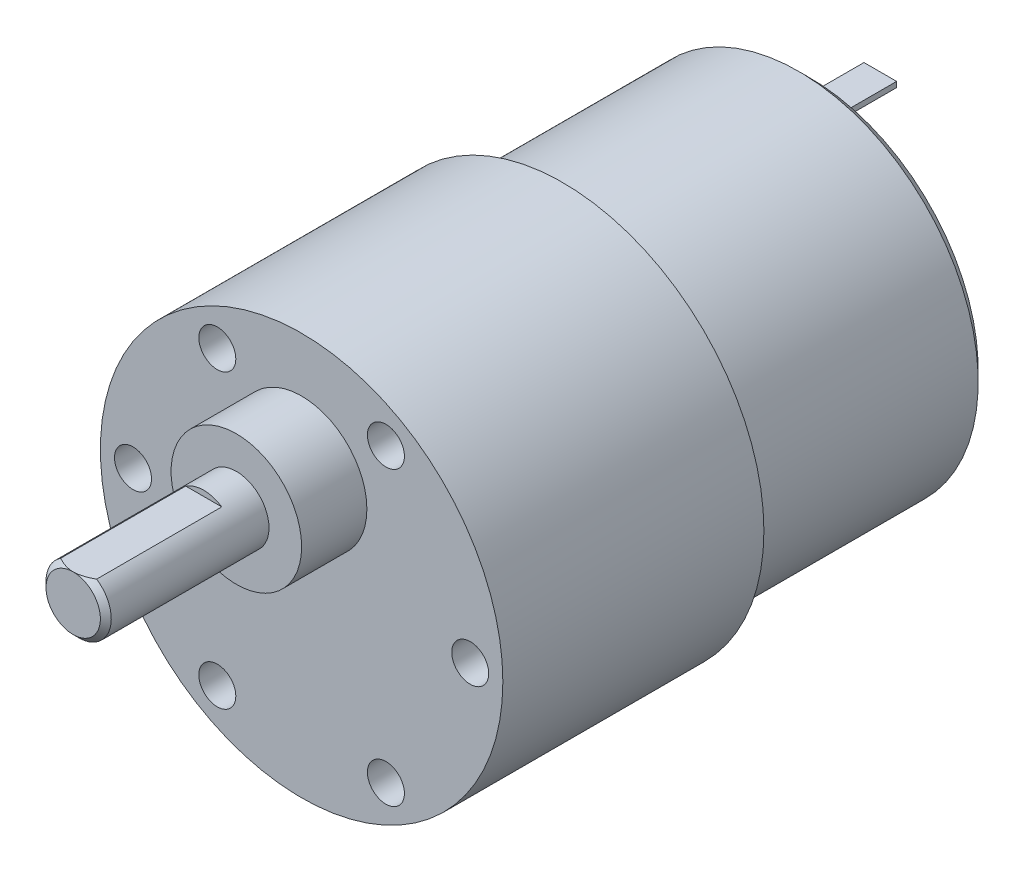
SolidWorks part; units mm, degrees
ref_plane "Front Plane" through (0, 0, 0) normal (0, 0, 1) x (1, 0, 0)
ref_plane "Top Plane" through (0, 0, 0) normal (0, 1, 0) x (1, 0, 0)
ref_plane "Right Plane" through (0, 0, 0) normal (1, 0, 0) x (0, 0, -1)
sketch "Sketch2" plane through (0, 0, 0) normal (0, 0, 1) x (1, 0, 0)
  circle A0 centre (0, 0) radius 18.5
  dimension "D1" = 37
extrude "Boss-Extrude1" add sketch "Sketch2" along normal blind 24
sketch "Sketch3" plane through (0, 0, 0) normal (0, 0, -1) x (-1, 0, 0)
  circle A0 centre (0, 0) radius 16.5
  dimension "D1" = 33
extrude "Boss-Extrude2" add sketch "Sketch3" along normal blind 22.7
sketch "Sketch4" plane through (0, 0, -22.7) normal (0, 0, -1) x (-1, 0, 0)
  circle A0 centre (0, 0) radius 3.75
  dimension "D1" = 7.5
extrude "Boss-Extrude3" add sketch "Sketch4" along normal blind 3.2
chamfer "Chamfer1" distance 1 angle 45 1 edges at (-16.5, 0, -22.7)
fillet "Fillet1" radius 1 1 edges at (-3.75, 0, -25.9)
sketch "Sketch5" plane through (0, 0, -22.7) normal (0, 0, -1) x (-1, 0, 0)
  line L0 (0, -12.45) -> (0, 12.45) construction
  line L2 (-1.5, 12.2) -> (1.5, 12.2)
  line L3 (-1.5, 12.2) -> (-1.5, 12.7)
  line L4 (-1.5, 12.7) -> (1.5, 12.7)
  line L5 (1.5, 12.2) -> (1.5, 12.7)
  line L6 (-1.5, 12.2) -> (1.5, 12.7) construction
  line L7 (-1.5, 12.7) -> (1.5, 12.2) construction
  line L8 (-1.5, -12.7) -> (1.5, -12.7)
  line L9 (-1.5, -12.7) -> (-1.5, -12.2)
  line L10 (-1.5, -12.2) -> (1.5, -12.2)
  line L11 (1.5, -12.7) -> (1.5, -12.2)
  line L12 (-1.5, -12.7) -> (1.5, -12.2) construction
  line L13 (-1.5, -12.2) -> (1.5, -12.7) construction
  point P4 (0, 0)
  dimension "D1" = 24.9
  dimension "D2" = 3
  dimension "D3" = 0.5
  dimension "D4" = 3
  dimension "D5" = 0.5
extrude "Boss-Extrude4" add sketch "Sketch5" along normal blind 6.5
sketch "Sketch6" plane through (0, 0, 24) normal (0, 0, 1) x (1, 0, 0)
  circle A0 centre (0, 7.5) radius 6
  circle A1 centre (0, 0) radius 18.5 construction
  point P4 (0, 0)
  dimension "D1" = 12
  dimension "D2" = 7.5
extrude "Boss-Extrude5" add sketch "Sketch6" along normal blind 6
sketch "Sketch7" plane through (0, 0, 30) normal (0, 0, 1) x (1, 0, 0)
  circle A0 centre (0, 7.5) radius 3
  dimension "D1" = 6
extrude "Boss-Extrude6" add sketch "Sketch7" along normal blind 15
sketch "Sketch8" plane through (0, 0, 45) normal (0, 0, 1) x (1, 0, 0)
  line L0 (-1.6583, 10) -> (1.6583, 10)
  circle A0 centre (0, 7.5) radius 3 construction
  circle A1 centre (0, 7.5) radius 3
  circle M3 centre (0, 7.5) radius 3
  dimension "D1" = 2.5
extrude "Cut-Extrude1" cut sketch "Sketch8" against normal blind 12 contours L0 M3 region at (0, 10.2015, 45)
chamfer "Chamfer2" distance 0.5 angle 45 1 edges at (0, 4.5, 45)
sketch "Sketch9" plane through (0, 0, 24) normal (0, 0, 1) x (1, 0, 0)
  line L0 (0, 0) -> (-15.5, 0) construction
  circle A0 centre (0, 0) radius 15.5 construction
  point P3 (-15.5, 0)
  dimension "D1" = 31
hole_wizard "M3 Clearance Hole1" positions "Sketch9" profile "Sketch10" hole size "M3" standard "ANSI Metric"
sketch "Sketch10" plane through (-15.5, 0, 24) normal (1, 0, 0) x (0, -1, 0)
  line L0 (0, 0) -> (0, 4.5215)
  line L1 (0, 4.5215) -> (1.7, 3.5)
  line L2 (1.7, 3.5) -> (1.7, 0)
  line L5 (1.7, 0) -> (0, 0)
  line L10 (0, 4.5215) -> (-1.7, 3.5) construction
  line L11 (0, -6.35) -> (0, 107.95) construction
  dimension "Hole Dia." = 3.4
  dimension "Hole Depth" = 3.5
  dimension "Drill Angle" = 118
pattern_circular "CirPattern1" count 6 over 360 about axis through (0, 0, 24) along (0, 0, -1) of "M3 Clearance Hole1"
